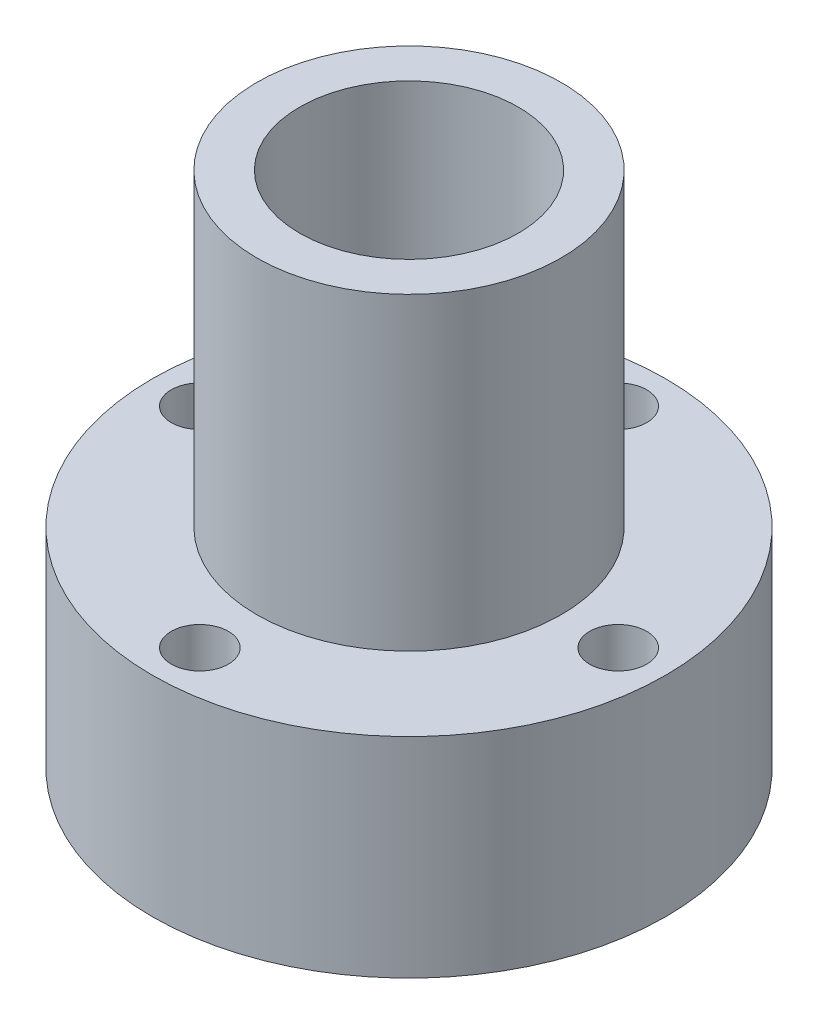
SolidWorks part; units mm, degrees
material "1023 Arkusz stali węglowej (SS)"
ref_plane "Płaszczyzna przednia" through (0, 0, 0) normal (0, 0, 1) x (1, 0, 0)
ref_plane "Płaszczyzna górna" through (0, 0, 0) normal (0, 1, 0) x (1, 0, 0)
ref_plane "Płaszczyzna prawa" through (0, 0, 0) normal (1, 0, 0) x (0, 0, -1)
sketch "Szkic1" plane through (0, 0, 0) normal (0, 0, 1) x (1, 0, 0)
  line L0 (0, 0) -> (0, -19.4689) construction
  line L1 (-16, 23.5) -> (-16, 56)
  line L2 (-11.5, 56) -> (-16, 56)
  line L3 (-11.5, 56) -> (-11.5, 0)
  line L4 (-27, 1.5) -> (-27, 23.5)
  line L5 (-27, 23.5) -> (-16, 23.5)
  line L6 (-15, 1.5) -> (-15, 0)
  line L7 (-27, 1.5) -> (-15, 1.5)
  line L8 (-11.5, 0) -> (-15, 0)
revolve "Obrót1" add sketch "Szkic1" angle 360 about L0
sketch "Szkic2" plane through (0, 23.5, 0) normal (0, 1, 0) x (1, 0, 0)
  circle A0 centre (0, 22) radius 3
  circle A1 centre (22, 0) radius 3
  circle A2 centre (0, -22) radius 3
  circle A3 centre (-22, 0) radius 3
  point P12 (0, 0)
  dimension "D2" = 6
  dimension "D1" = 22
  dimension "D3" = 4
extrude "Wytnij-wyciągnięcie1" cut sketch "Szkic2" against normal through all
